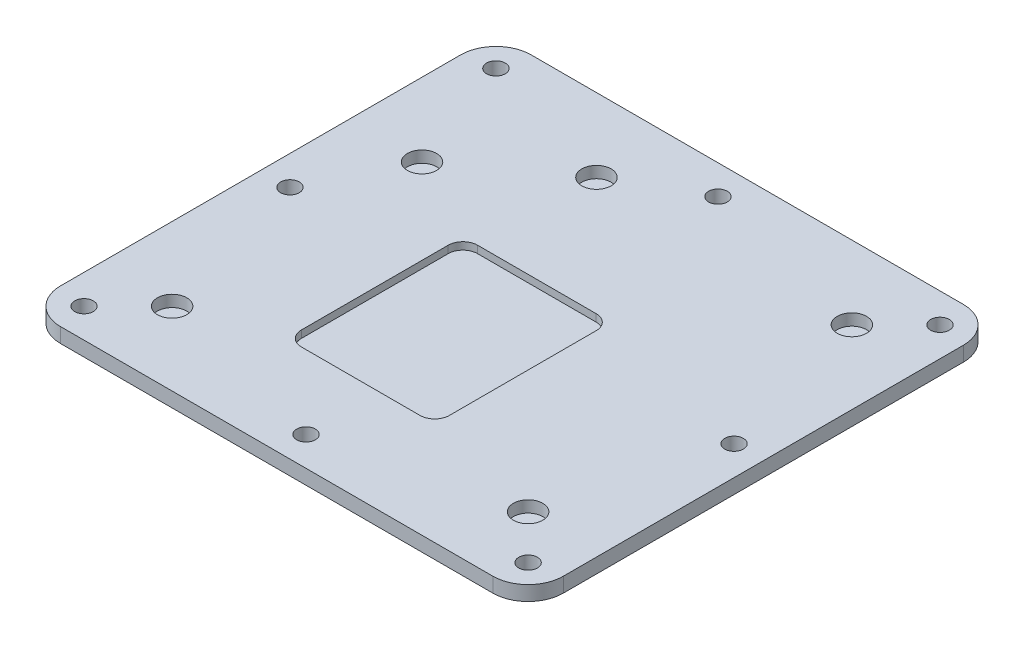
SolidWorks part; units mm, degrees
note: The reader was unsure of these and kept them because the rebuilt part matched: shared geometry of "Sketch1<4>".
material "Nylon 6/10"
ref_plane "Front Plane" through (0, 0, 0) normal (0, 0, 1) x (1, 0, 0)
ref_plane "Top Plane" through (0, 0, 0) normal (0, 1, 0) x (1, 0, 0)
ref_plane "Right Plane" through (0, 0, 0) normal (1, 0, 0) x (0, 0, -1)
sketch "Sketch1" plane through (0, 0, 0) normal (0, 1, 0) x (1, 0, 0)
  line L0 (-41.656, 22.1996) -> (-19.9136, 22.1996) construction
  line L5 (41.656, -38.1762) -> (-41.656, -38.1762) construction
  line L6 (41.656, -38.1762) -> (41.656, 38.1762) construction
  line L7 (41.656, 38.1762) -> (-41.656, 38.1762) construction
  line L8 (-41.656, -38.1762) -> (-41.656, 38.1762) construction
  line L9 (41.656, -38.1762) -> (-41.656, 38.1762) construction
  line L10 (41.656, 38.1762) -> (-41.656, -38.1762) construction
  line L11 (-19.9136, 22.1996) -> (-19.9136, 38.1762) construction
  line L12 (-54.356, -50.8762) -> (-54.356, 50.8762)
  line L13 (54.356, 50.8762) -> (-54.356, 50.8762)
  line L14 (54.356, -50.8762) -> (54.356, 50.8762)
  line L15 (54.356, -50.8762) -> (-54.356, -50.8762)
  line L17 (11.938, -28.6512) -> (-20.066, -28.6512)
  line L18 (11.938, -28.6512) -> (11.938, 9.4488)
  line L19 (11.938, 9.4488) -> (-20.066, 9.4488)
  line L20 (-20.066, -28.6512) -> (-20.066, 9.4488)
  line L21 (11.938, -28.6512) -> (-20.066, 9.4488) construction
  line L22 (11.938, 9.4488) -> (-20.066, -28.6512) construction
  point P0 (0, 0)
  point P5 (-38.481, -35.0012)
  point P14 (-4.064, -9.6012)
  point P19 (-16.7386, -35.0012)
  point P20 (-10.7442, -35.0012)
  point P21 (38.481, -35.0012)
  point P22 (-16.7386, 35.0012)
  point P23 (-10.7442, 35.0012)
  point P24 (-38.481, 19.0246)
  point P25 (38.481, 35.0012)
  dimension "D1" = 83.312
  dimension "D2" = 76.3524
  dimension "D3" = 21.7424
  dimension "D4" = 15.9766
  dimension "D6" = 32.004
  dimension "D7" = 38.1
  dimension "D8" = 19.05
  dimension "D9" = 21.59
  dimension "D10" = 3.175
  dimension "D11" = 3.175
  dimension "D12" = 24.9174
  dimension "D13" = 30.9118
  dimension "D14" = 80.137
  dimension "D15" = 57.2008
  dimension "D16" = 73.1774
  dimension "D5" = 12.7
extrude "Boss-Extrude1" add sketch "Sketch1" against normal blind 3.175 contours L20 L17 L18 L19 | L15 L14 L13 L12 L17 L20 L19 L18
extrude "Cut-Extrude1" cut sketch "Sketch1<4>" against normal blind 1.5875 contours L20 L17 L18 L19
sketch "Sketch1<4>" plane through (0, 0, 0) normal (0, 1, 0) x (1, 0, 0) same geometry as "Sketch1"
hole_wizard "M2.5x0.45 Tapped Hole1" [suppressed] positions "Sketch2" profile "Sketch3" tap size "M2.5x0.45" standard "ANSI Metric"
sketch "Sketch2" plane through (0, 0, 0) normal (0, 1, 0) x (1, 0, 0)
  point P0 (-38.481, -35.0012)
  point P9 (38.481, -35.0012)
  point P13 (-38.481, 19.0246)
  point P16 (-16.7386, 35.0012)
  point P19 (38.481, 35.0012)
sketch "Sketch3" plane through (-38.481, 0, 35.0012) normal (1, 0, 0) x (0, 0, 1)
  line L0 (0, 0) -> (0, 3.175)
  line L1 (0, 3.175) -> (1.025, 3.175)
  line L2 (1.025, 3.175) -> (1.025, 0)
  line L5 (1.025, 0) -> (0, 0)
  line L11 (0, -6.35) -> (0, 107.95) construction
  dimension "Thru Tap Drill Dia." = 2.05
  dimension "Thru Tap Drill Depth" = 3.175
cosmetic thread "Hole Thread1" [suppressed] parameters "D2"=2.5
cosmetic thread "Hole Thread2" [suppressed] parameters "D2"=2.5
cosmetic thread "Hole Thread3" [suppressed] parameters "D2"=2.5
cosmetic thread "Hole Thread4" [suppressed] parameters "D2"=2.5
cosmetic thread "Hole Thread5" [suppressed] parameters "D2"=2.5
sketch "Sketch4" plane through (0, 0, 0) normal (0, 1, 0) x (1, 0, 0)
  circle A0 centre (-38.481, 19.0246) radius 3.175
  circle A1 centre (-16.7386, 35.0012) radius 3.175
  circle A2 centre (38.481, 35.0012) radius 3.175
  circle A3 centre (38.481, -35.0012) radius 3.175
  circle A4 centre (-38.481, -35.0012) radius 3.175
  dimension "D1" = 6.35
extrude "Cut-Extrude2" cut sketch "Sketch4" against normal blind 2.5
fillet "Fillet1" radius 7.62 4 edges at (-54.356, -1.5875, -50.8762) (54.356, -1.5875, -50.8762) (54.356, -1.5875, 50.8762) (-54.356, -1.5875, 50.8762)
hole_wizard "#10-32 Tapped Hole1" positions "Sketch5" profile "Sketch6" tap size "#10-32" standard "ANSI Inch" end condition through all
sketch "Sketch5" plane through (0, 0, 0) normal (0, 1, 0) x (1, 0, 0)
  line L0 (54.356, 50.8762) -> (-54.356, 50.8762) construction
  line L1 (-54.356, -50.8762) -> (-54.356, 50.8762) construction
  line L2 (54.356, -50.8762) -> (-54.356, -50.8762) construction
  line L3 (54.356, -50.8762) -> (54.356, 50.8762) construction
  point P0 (-48.006, 44.5262)
  point P2 (48.006, 44.5262)
  point P4 (48.006, -44.5262)
  point P6 (-48.006, -44.5262)
  point P8 (0, -44.5262)
  point P10 (-48.006, 0)
  point P12 (48.006, 0)
  point P14 (0, 44.5262)
  dimension "D1" = 6.35
  dimension "D2" = 6.35
  dimension "D3" = 6.35
  dimension "D4" = 6.35
sketch "Sketch6" plane through (-48.006, 0, -44.5262) normal (1, 0, 0) x (0, 0, 1)
  line L0 (0, 0) -> (0, 3.175)
  line L1 (0, 3.175) -> (2.0193, 3.175)
  line L2 (2.0193, 3.175) -> (2.0193, 0)
  line L5 (2.0193, 0) -> (0, 0)
  line L11 (0, -6.35) -> (0, 107.95) construction
  dimension "Thru Tap Drill Dia." = 4.0386
  dimension "Thru Tap Drill Depth" = 3.175
cosmetic thread "Hole Thread6" parameters "D2"=4.826
cosmetic thread "Hole Thread7" parameters "D2"=4.826
cosmetic thread "Hole Thread8" parameters "D2"=4.826
cosmetic thread "Hole Thread9" parameters "D2"=4.826
cosmetic thread "Hole Thread10" parameters "D2"=4.826
cosmetic thread "Hole Thread11" parameters "D2"=4.826
cosmetic thread "Hole Thread12" parameters "D2"=4.826
cosmetic thread "Hole Thread13" parameters "D2"=4.826
fillet "Fillet2" radius 3.175 4 edges at (-20.066, -0.7937, -9.4488) (11.938, -0.7937, -9.4488) (11.938, -0.7937, 28.6512) (-20.066, -0.7937, 28.6512)
